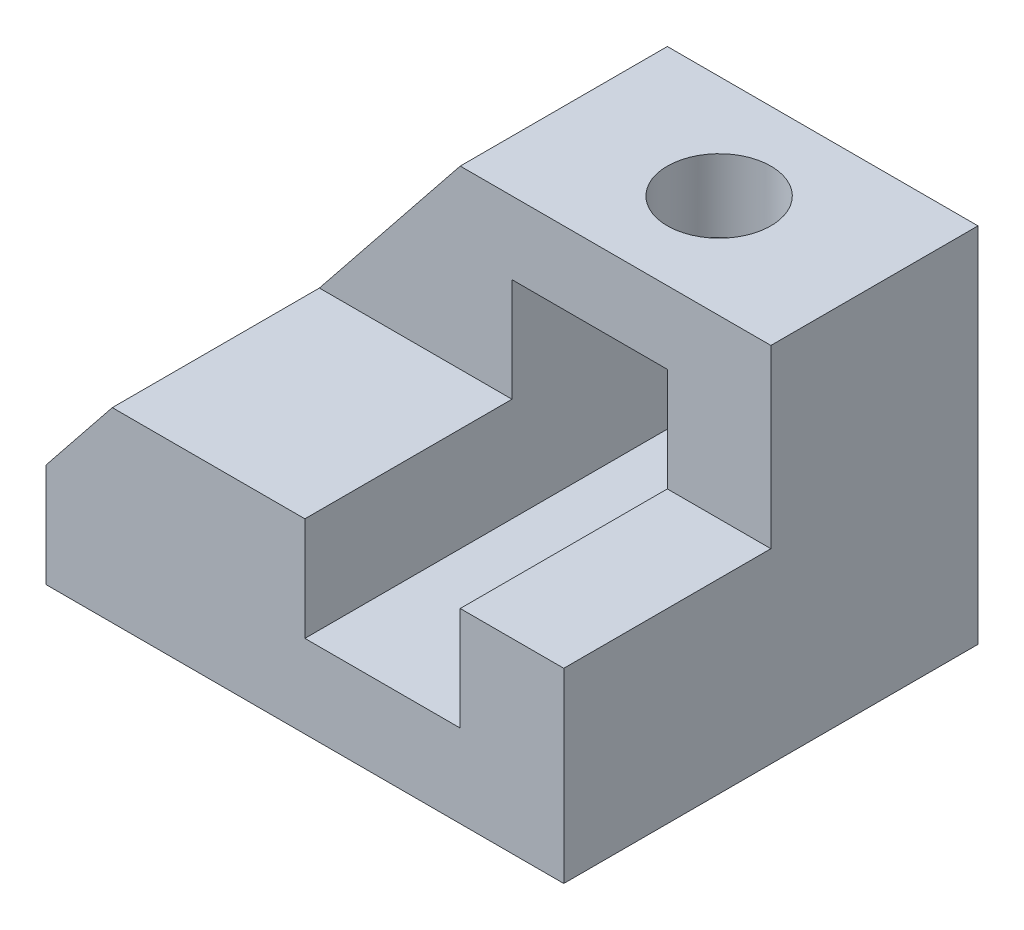
SolidWorks part; units mm, degrees
ref_plane "Front Plane" through (0, 0, 0) normal (0, 0, 1) x (1, 0, 0)
ref_plane "Top Plane" through (0, 0, 0) normal (0, 1, 0) x (1, 0, 0)
ref_plane "Right Plane" through (0, 0, 0) normal (1, 0, 0) x (0, 0, -1)
sketch "Sketch1" plane through (0, 0, 0) normal (0, 0, 1) x (1, 0, 0)
  line L0 (0, 0) -> (50, 0)
  line L1 (50, 0) -> (50, 35)
  line L2 (50, 35) -> (20, 35)
  line L3 (20, 35) -> (0, 10)
  line L4 (0, 10) -> (0, 0)
  line L5 (6.4, 18) -> (50, 18)
  line L7 (25, 28) -> (40, 28)
  line L8 (25, 28) -> (25, 8)
  line L9 (25, 8) -> (40, 8)
  line L10 (40, 28) -> (40, 8)
  dimension "D1" = 50
  dimension "D2" = 35
  dimension "D3" = 30
  dimension "D4" = 10
  dimension "D5" = 18
  dimension "D6" = 15
  dimension "D7" = 25
  dimension "D8" = 20
  dimension "D9" = 8
extrude "Boss-Extrude1" add sketch "Sketch1" along normal blind 40 contours L5 L10 L9 L8 L3 L4 L0 L1 region at (24.2551, 7.9479, 0)
extrude "Boss-Extrude2" add sketch "Sketch1<4>" along normal blind 20 contours L7 L10 L5 L1 L2 L3 L8 region at (45, 18.468, 0)
sketch "Sketch1<4>" plane through (0, 0, 0) normal (0, 0, 1) x (1, 0, 0) same geometry as "Sketch1"
sketch "Sketch2" plane through (0, 35, 0) normal (0, 1, 0) x (1, 0, 0)
  line L4 (50, 0) -> (20, 0)
  line L5 (20, 0) -> (20, -20)
  line L6 (20, -20) -> (50, -20)
  line L7 (50, -20) -> (50, 0)
  line L8 (50, 0) -> (20, 0)
  line L9 (20, 0) -> (20, -20)
  line L10 (20, -20) -> (50, -20)
  line L11 (50, -20) -> (50, 0)
  circle A0 centre (35, -10) radius 5
  dimension "D2" = 10
  dimension "D3" = 15
  dimension "D4" = 10
  dimension "D1" = 0
extrude "Cut-Extrude1" cut sketch "Sketch2" against normal through all contours A0
